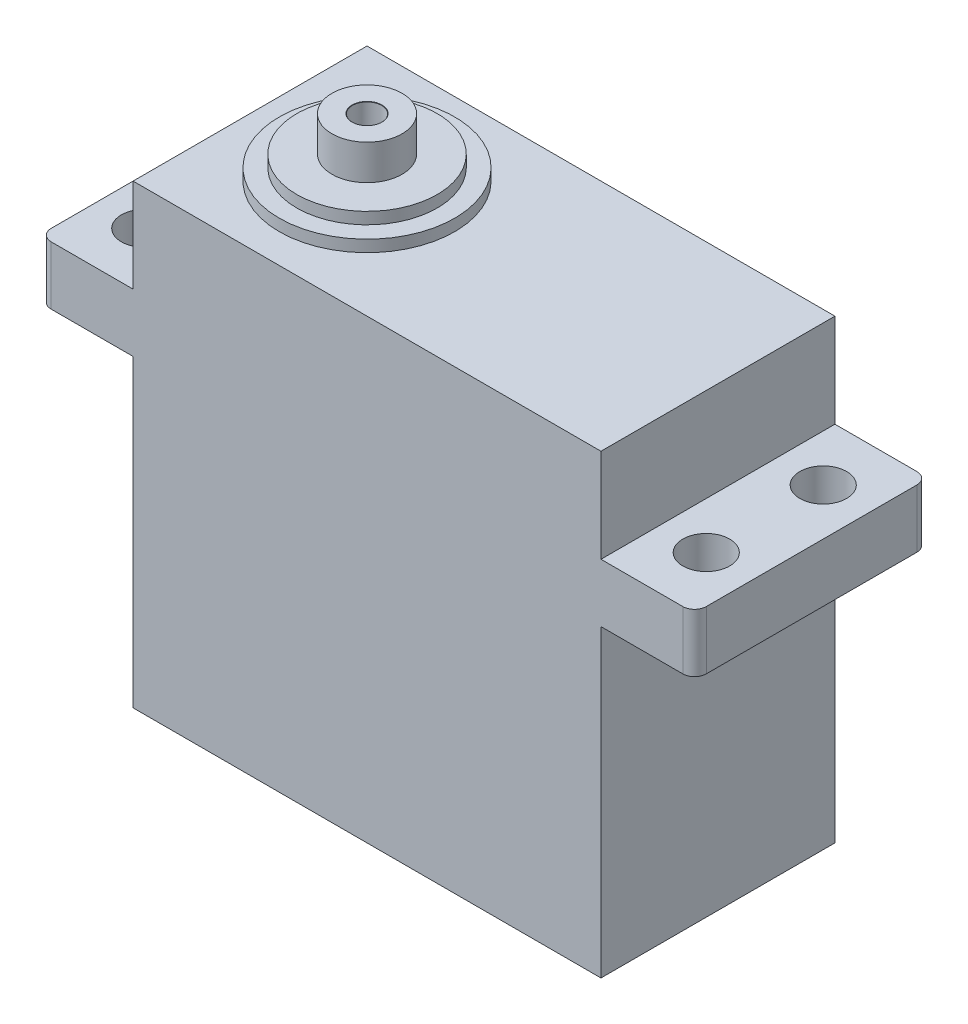
SolidWorks part; units mm, degrees
ref_plane "前视基准面" through (0, 0, 0) normal (0, 0, 1) x (1, 0, 0)
ref_plane "上视基准面" through (0, 0, 0) normal (0, 1, 0) x (1, 0, 0)
ref_plane "右视基准面" through (0, 0, 0) normal (1, 0, 0) x (0, 0, -1)
other "Configuration Table"
sketch "草图1" plane through (0, 0, 0) normal (0, 0, 1) x (1, 0, 0)
  line L0 (20, 39) -> (20, 0) construction
  line L1 (0, 0) -> (40, 0)
  line L2 (0, 0) -> (0, 39)
  line L3 (0, 39) -> (40, 39)
  line L4 (40, 0) -> (40, 39)
  line L5 (0, 26.0156) -> (-8, 26.0156)
  line L6 (0, 26.0156) -> (0, 31)
  line L7 (0, 31) -> (-8, 31)
  line L8 (-8, 26.0156) -> (-8, 31)
  line L9 (40, 26.0156) -> (48, 26.0156)
  line L10 (48, 26.0156) -> (48, 31)
  line L11 (40, 31) -> (48, 31)
  dimension "D1" = 40
  dimension "D2" = 39
  dimension "D3" = 31
extrude "凸台-拉伸1" add sketch "草图1" along normal blind 20 contours L3 L0 L1 L4 | L0 L3 L2 L1 | L11 L4 L9 L10 | L8 L7 L6 L5 region at (30, 19.5, 0) region at (10, 19.5, 0) region at (44, 28.5078, 0)
sketch "草图2" plane through (0, 39, 0) normal (0, 1, 0) x (1, 0, 0)
  line L0 (0, -10) -> (40, -10) construction
  line L1 (0, -20) -> (0, 0) construction
  line L2 (40, -20) -> (40, 0) construction
  line L3 (20, 0) -> (20, -20) construction
  line L4 (0, 0) -> (40, 0) construction
  line L5 (0, -20) -> (40, -20) construction
  line L6 (-4, 0) -> (-4, -20) construction
  line L7 (0, 0) -> (-8, 0) construction
  line L8 (0, -20) -> (-8, -20) construction
  line L9 (0, -10) -> (-8, -10) construction
  line L10 (-8, -20) -> (-8, 0) construction
  line L11 (-8, -10) -> (48, -10) construction
  line L12 (48, -20) -> (48, 0) construction
  circle A1 centre (10, -10) radius 7.5
  circle A2 centre (10, -10) radius 6
  circle A3 centre (10, -10) radius 3
  circle A4 centre (-4, -5) radius 2
  circle A5 centre (44, -5) radius 2
  circle A6 centre (44, -15) radius 2
  circle A7 centre (-4, -15) radius 2
  point P32 (-8, 0)
  dimension "D1" = 15
  dimension "D2" = 12
  dimension "D3" = 6
  dimension "D4" = 4
  dimension "D5" = 14
  dimension "D6" = 5
extrude "切除-拉伸1" cut sketch "草图2" against normal blind 20 contours A7 region at (-4, 39, 15)
extrude "切除-拉伸2" cut sketch "草图2<3>" against normal blind 20 contours A4 | A5 | A6 region at (-4, 39, 5) region at (44, 39, 5) region at (44, 39, 15)
sketch "草图2<3>" plane through (0, 39, 0) normal (0, 1, 0) x (1, 0, 0) same geometry as "草图2"
extrude "凸台-拉伸2" add sketch "草图2<4>" along normal blind 1 contours A1
sketch "草图2<4>" plane through (0, 39, 0) normal (0, 1, 0) x (1, 0, 0) same geometry as "草图2"
extrude "凸台-拉伸3" add sketch "草图2<5>" along normal blind 2 contours A2
sketch "草图2<5>" plane through (0, 39, 0) normal (0, 1, 0) x (1, 0, 0) same geometry as "草图2"
extrude "凸台-拉伸4" add sketch "草图2<6>" along normal blind 5 contours A3
sketch "草图2<6>" plane through (0, 39, 0) normal (0, 1, 0) x (1, 0, 0) same geometry as "草图2"
hole_wizard "M3 螺纹孔的螺纹孔钻头2" positions "3D草图2" profile "草图4" hole size "M3" standard "GB"
sketch3d "3D草图2"
  line L0 (10, 44, 10) -> (10, 41, 10) construction
  point P0 (10, 44, 10)
sketch "草图4" plane through (10, 44, 10) normal (1, 0, 0) x (0, 0, 1)
  line L0 (0, 0) -> (0, 2)
  line L1 (0, 2) -> (1.25, 2)
  line L2 (1.25, 2) -> (1.25, 0.025)
  line L3 (1.25, 0.025) -> (1.275, 0)
  line L5 (1.275, 0) -> (0, 0)
  line L6 (-1.25, 0.025) -> (-1.275, 0) construction
  line L10 (0, 2) -> (-1.25, 2) construction
  line L11 (0, -6.35) -> (0, 107.95) construction
  dimension "孔直径" = 2.5
  dimension "孔深度" = 2
  dimension "近端锥形沉头孔直径" = 2.55
  dimension "近端锥形沉头孔角度" = 90
  dimension "导头角度" = 180
fillet "圆角1" radius 1 1 edges at (-8, 28.5078, 20)
fillet "圆角2" radius 1 3 edges at (-8, 28.5078, 0) (48, 28.5078, 0) (48, 28.5078, 20)
